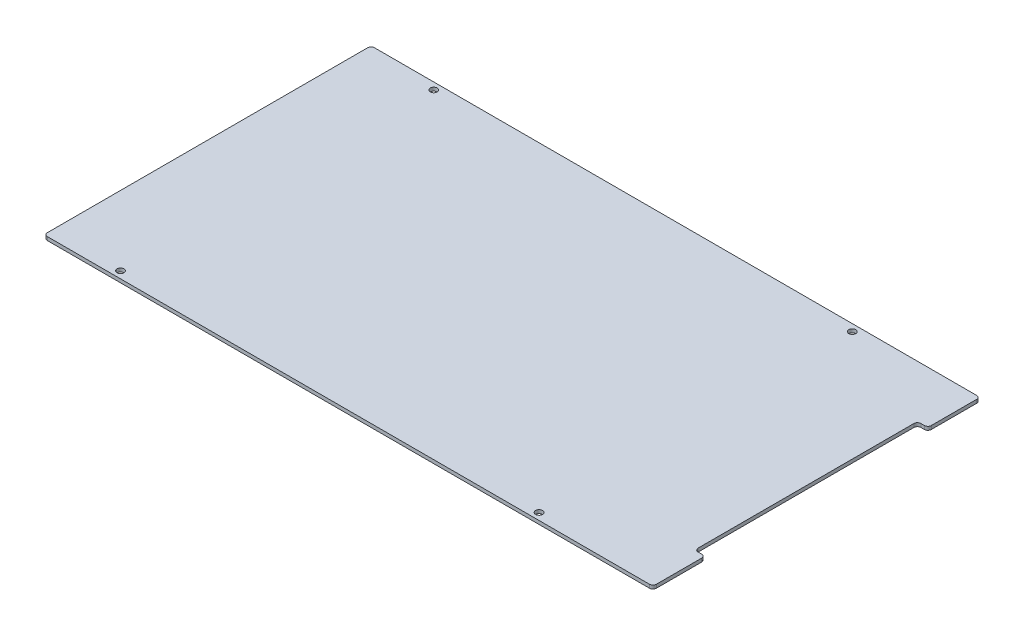
SolidWorks part; units mm, degrees
ref_plane "Front Plane" through (0, 0, 0) normal (0, 0, 1) x (1, 0, 0)
ref_plane "Top Plane" through (0, 0, 0) normal (0, 1, 0) x (1, 0, 0)
ref_plane "Right Plane" through (0, 0, 0) normal (1, 0, 0) x (0, 0, -1)
sketch "Sketch1" plane through (0, 0, 0) normal (0, 1, 0) x (1, 0, 0)
  line L1 (-277.8125, -149.225) -> (277.8125, -149.225)
  line L2 (-277.8125, -149.225) -> (-277.8125, 149.225)
  line L3 (-277.8125, 149.225) -> (277.8125, 149.225)
  line L4 (277.8125, -149.225) -> (277.8125, 149.225)
  line L5 (-277.8125, -149.225) -> (277.8125, 149.225) construction
  line L6 (-277.8125, 149.225) -> (277.8125, -149.225) construction
  point P0 (0, 0)
  dimension "D1" = 555.625
  dimension "D2" = 298.45
extrude "Boss-Extrude1" add sketch "Sketch1" along normal blind 3.175
sketch "Sketch2" plane through (0, 3.175, 0) normal (0, 1, 0) x (1, 0, 0)
  line L0 (277.8125, -149.225) -> (277.8125, 149.225) construction
  line L1 (277.8125, 101.6) -> (268.2875, 101.6)
  line L2 (277.8125, 101.6) -> (277.8125, -101.6)
  line L3 (277.8125, -101.6) -> (268.2875, -101.6)
  line L4 (268.2875, 101.6) -> (268.2875, -101.6)
  point P6 (268.2875, 0)
  dimension "D1" = 203.2
  dimension "D2" = 9.525
extrude "Cut-Extrude1" cut sketch "Sketch2" against normal through all
fillet "Fillet1" radius 3.175 2 edges at (268.2875, 1.5875, 101.6) (268.2875, 1.5875, -101.6)
hole_wizard "1/4 (0.25) Diameter Hole1" positions "Sketch3" profile "Sketch4" hole size "1/4" standard "ANSI Inch" end condition through all
sketch "Sketch3" plane through (0, 0, 0) normal (0, -1, 0) x (-1, 0, 0)
  line L0 (277.8125, -149.225) -> (-277.8125, -149.225) construction
  line L1 (-277.8125, -149.225) -> (-277.8125, -101.6) construction
  line L2 (277.8125, 149.225) -> (277.8125, -149.225) construction
  point P0 (-167.5765, -142.875)
  point P2 (214.3125, -142.875)
  dimension "D1" = 6.35
  dimension "D2" = 110.236
  dimension "D3" = 63.5
  dimension "D4" = 381.889
sketch "Sketch4" plane through (167.5765, 0, 142.875) normal (1, 0, 0) x (0, 0, -1)
  line L0 (0, 0) -> (0, 3.175)
  line L1 (0, 3.175) -> (3.175, 3.175)
  line L2 (3.175, 3.175) -> (3.175, 0)
  line L5 (3.175, 0) -> (0, 0)
  line L11 (0, -6.35) -> (0, 107.95) construction
  dimension "Thru Hole Dia." = 6.35
  dimension "Thru Hole Depth" = 3.175
mirror "Mirror1" about plane through (0, 0, 0) normal (0, 0, 1) of "1/4 (0.25) Diameter Hole1"
fillet "Fillet2" radius 3.175 6 edges at (277.8125, 1.5875, -101.6) (277.8125, 1.5875, 101.6) (277.8125, 1.5875, -149.225) (-277.8125, 1.5875, -149.225) (277.8125, 1.5875, 149.225) (-277.8125, 1.5875, 149.225)
